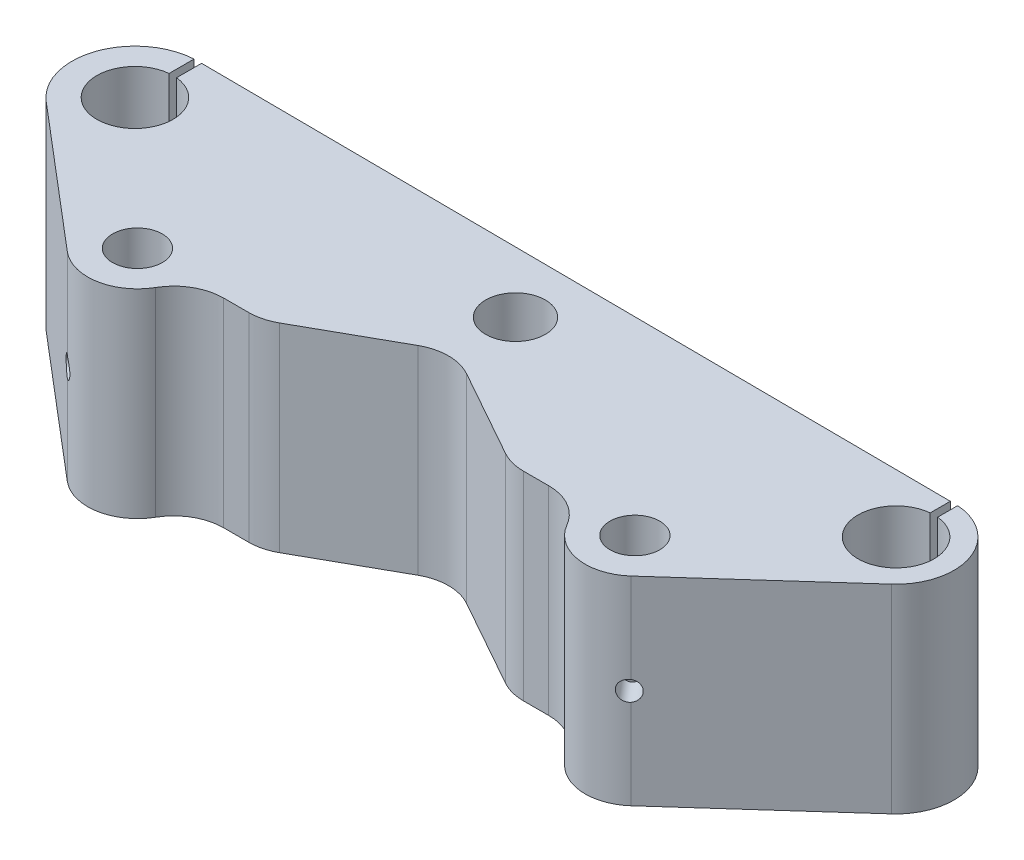
SolidWorks part; units mm, degrees
ref_plane "Płaszczyzna przednia" through (0, 0, 0) normal (0, 0, 1) x (1, 0, 0)
ref_plane "Płaszczyzna górna" through (0, 0, 0) normal (0, 1, 0) x (1, 0, 0)
ref_plane "Płaszczyzna prawa" through (0, 0, 0) normal (1, 0, 0) x (0, 0, -1)
sketch "Szkic1" plane through (0, 0, 0) normal (0, 1, 0) x (1, 0, 0)
  line L0 (-76.5, 12.65) -> (76.5761, 11.6498)
  line L1 (-84.6922, -9.639) -> (-56.476, -33.6198)
  line L2 (56.6792, -33.4423) -> (84.2813, -8.6703)
  line L3 (-50, -36) -> (50, -36)
  line L4 (-40, -26) -> (40, -26)
  circle A0 centre (-76.5, 0) radius 7.65
  circle A1 centre (76.5, 0) radius 7.65
  circle A2 centre (-76.5, 0) radius 12.65
  circle A3 centre (76.5, 0) radius 11.65
  circle A4 centre (0, 0) radius 6
  circle A5 centre (-50, -26) radius 5
  circle A6 centre (50, -26) radius 5
  circle A7 centre (-50, -26) radius 10
  circle A8 centre (50, -26) radius 10
  dimension "D1" = 15.3
  dimension "D2" = 15.3
  dimension "D7" = 12
  dimension "D8" = 10
  dimension "D9" = 100
  dimension "D3" = 153
  dimension "D4" = 76.5
  dimension "D10" = 50
  dimension "D11" = 26
  dimension "D5" = 5
  dimension "D6" = 4
  dimension "D12" = 5
extrude "Dodanie-wyciągnięcie1" add sketch "Szkic1" along normal blind 40 contours A2 A0 | A8 L2 A3 L0 A2 L1 A7 L3 A4 | A7 A5 | A8 A6 | A3 A1 region at (-76.4197, 0, -12.2917) region at (-0.0031, 0, 6.5837) region at (84.5309, 0, -7.9786) region at (-54.0789, 0, 17.1804) region at (53.475, 0, 35.0746)
sketch "Szkic2" plane through (0, 0, 0) normal (0, -1, 0) x (1, 0, 0)
  circle A0 centre (0, 0) radius 11
  dimension "D1" = 22
extrude "Wytnij-wyciągnięcie1" cut sketch "Szkic2" against normal blind 5
sketch "Szkic3" plane through (0, 5, 0) normal (0, -1, 0) x (1, 0, 0)
  line L0 (0, 0) -> (-5.6569, 5.6569) construction
  line L1 (0, 0) -> (0, 9.4855) construction
  circle A0 centre (0, 0) radius 8 construction
  circle A1 centre (-5.6569, 5.6569) radius 1.25
  circle A2 centre (5.6569, 5.6569) radius 1.25
  circle A3 centre (5.6569, -5.6569) radius 1.25
  circle A4 centre (-5.6569, -5.6569) radius 1.25
  point P15 (0, 0)
  dimension "D1" = 16
  dimension "D2" = 2.5
  dimension "D3" = 45
  dimension "D4" = 4
extrude "Wytnij-wyciągnięcie2" cut sketch "Szkic3" against normal blind 10
sketch "Szkic4" plane through (0, 40, 0) normal (0, 1, 0) x (1, 0, 0)
  line L0 (-25, -26) -> (0, -12)
  line L1 (-40, -26) -> (40, -26) construction
  line L2 (0, -12) -> (25, -26)
  line L3 (25, -26) -> (-25, -26)
  dimension "D1" = 14
  dimension "D2" = 50
extrude "Wytnij-wyciągnięcie3" cut sketch "Szkic4" against normal through all
fillet "Zaokrąglenie1" radius 10 5 edges at (40, 20, 26) (-40, 20, 26) (25, 20, 26) (0, 20, 12) (-25, 20, 26)
sketch "Szkic5" plane through (-40.2754, 0, 47.3886) normal (-0.6476, 0, 0.762) x (0.762, 0, 0.6476)
  line L0 (-16.2613, 40) -> (-26.2613, 40) construction
  line L1 (-16.2613, 40) -> (-26.2613, 40)
  line L2 (-21.2613, 40) -> (-21.2613, 0) construction
  circle A0 centre (-21.2613, 20) radius 2
  dimension "D1" = 4
extrude "Wytnij-wyciągnięcie4" cut sketch "Szkic5" against normal blind 20 contours A0
mirror "Lustro1" about plane through (0, 0, 0) normal (1, 0, 0) of "Wytnij-wyciągnięcie4"
sketch "Szkic6" plane through (0, 40, 0) normal (0, 1, 0) x (1, 0, 0)
  line L0 (0, 0) -> (0, 20.6321) construction
  line L1 (-75.75, 7.6131) -> (-75.75, 16.4542)
  line L2 (-75.75, 16.4542) -> (-77.25, 16.4542)
  line L3 (-77.25, 16.4542) -> (-77.25, 7.6131)
  line L4 (77.25, 16.4542) -> (77.25, 7.6131)
  line L5 (75.75, 16.4542) -> (77.25, 16.4542)
  line L6 (75.75, 7.6131) -> (75.75, 16.4542)
  circle A0 centre (76.5, 0) radius 7.65 construction
  circle A1 centre (-76.5, 0) radius 7.65 construction
  circle A2 centre (76.5, 0) radius 7.65
  circle A3 centre (-76.5, 0) radius 7.65
  arc M10 (84.2813, -8.6703) -> (76.5761, 11.6498) centre (76.5, 0) ccw
  line M11 (76.5761, 11.6498) -> (-76.5, 12.65)
  arc M12 (-76.5, 12.65) -> (-84.6922, -9.639) centre (-76.5, 0) ccw
  circle M20 centre (-76.5, 0) radius 7.65
  circle M23 centre (76.5, 0) radius 7.65
  dimension "D1" = 0.75
  dimension "D2" = 1.5
extrude "Wytnij-wyciągnięcie5" cut sketch "Szkic6" against normal through all contours L3 L1 M12 M20 M11 | L6 L4 M23 M10 M11 region at (-76.4997, 40, -10.1414) region at (76.4993, 40, -9.6425)
